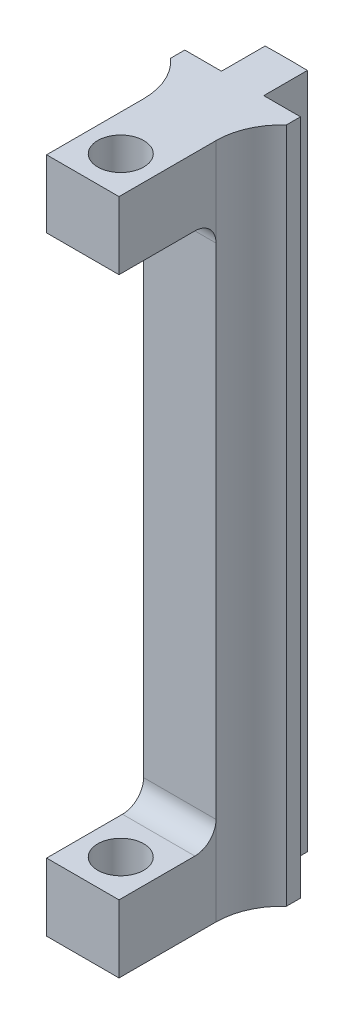
SolidWorks part; units mm, degrees
ref_plane "Front Plane" through (0, 0, 0) normal (0, 0, 1) x (1, 0, 0)
ref_plane "Top Plane" through (0, 0, 0) normal (0, 1, 0) x (1, 0, 0)
ref_plane "Right Plane" through (0, 0, 0) normal (1, 0, 0) x (0, 0, -1)
sketch "Sketch1" plane through (0, 0, 0) normal (0, 1, 0) x (1, 0, 0)
  line L0 (-2.7181, 75.8155) -> (2.7181, 75.8155)
  line L1 (8.1401, 80.7182) -> (8.1401, 83.4238)
  line L2 (-8.1401, 80.7182) -> (-8.1401, 83.4238)
  line L3 (0, 75.8155) -> (0, 87.8958) construction
  line L4 (2.7181, 75.8155) -> (2.7181, 62.9548) construction
  arc A0 (2.7181, 75.8155) -> (8.1401, 80.7182) centre (7.6457, 75.8155) cw
  arc A1 (8.1401, 83.4238) -> (-8.1401, 83.4238) centre (0, 0) ccw
  arc A2 (-2.7181, 75.8155) -> (-8.1401, 80.7182) centre (-7.6457, 75.8155) ccw
  arc A3 (8.1401, 80.7182) -> (20.3966, 78.5217) centre (0, 0) cw construction
  dimension "D2" = 81.1276
  dimension "D3" = 83.82
  dimension "D4" = 4.9276
  dimension "D1" = 2.7181
extrude "Boss-Extrude1" add sketch "Sketch1" against normal blind 50.8
sketch "Sketch3" plane through (0, 0, 0) normal (0, 1, 0) x (1, 0, 0)
  line L0 (-4.3408, 80.5281) -> (-1.5875, 80.5281)
  line L1 (-2.7181, 75.8155) -> (2.7181, 75.8155) construction
  line L2 (0, 83.82) -> (0, 75.8155) construction
  line L3 (-4.3408, 80.5281) -> (-4.3408, 76.768)
  line L4 (-4.3408, 76.768) -> (-9.7396, 76.768)
  line L5 (-9.7396, 76.768) -> (-9.7396, 86.1044)
  line L6 (-4.5117, 83.6985) -> (-4.3408, 80.5281) construction
  line L7 (-4.5117, 83.6985) -> (46.925, 86.4711) construction
  line L8 (0, 83.82) -> (-1.5875, 83.82)
  line L9 (-3.175, 86.1044) -> (-9.7396, 86.1044)
  line L10 (-1.5875, 83.82) -> (-1.5875, 80.5281)
  arc A0 (8.1401, 83.4238) -> (-8.1401, 83.4238) centre (0, 0) ccw construction
  arc A1 (-2.7181, 75.8155) -> (-8.1401, 80.7182) centre (-7.6457, 75.8155) ccw construction
  point P14 (-4.3408, 79.4704)
  dimension "D1" = 3.175
  dimension "D2" = 1.5875
extrude "Cut-Extrude1" cut sketch "Sketch3" against normal through all
mirror "Mirror2" about plane through (0, 0, 0) normal (1, 0, 0) of "Cut-Extrude1"
sketch "Sketch2" plane through (0, 0, 0) normal (0, 1, 0) x (1, 0, 0)
  line L1 (2.7181, 75.8155) -> (-2.7181, 75.8155)
  line L2 (2.7181, 75.8155) -> (2.7181, 68.5315)
  line L3 (2.7181, 68.5315) -> (-2.7181, 68.5315)
  line L4 (-2.7181, 75.8155) -> (-2.7181, 68.5315)
  dimension "D1" = 7.2839
extrude "Boss-Extrude2" add sketch "Sketch2" against normal blind 5.08
fillet "Fillet1" radius 1.5875 1 edges at (0, -5.08, -75.8155)
ref_plane "midplane" through (0, -25.4, 0) normal (0, -1, 0) x (-1, 0, 0)
mirror "Mirror1" about plane through (0, -25.4, 0) normal (0, -1, 0) of "Boss-Extrude2", "Fillet1"
hole_wizard "#4 Clearance Hole1" positions "Sketch4" profile "Sketch5" hole size "#4" standard "ANSI Inch" end condition through all
sketch "Sketch4" plane through (0, 0, 0) normal (0, 1, 0) x (1, 0, 0)
  line L0 (0, 68.5315) -> (0, 74.228) construction
  line L2 (-2.7181, 68.5315) -> (2.7181, 68.5315) construction
  line L3 (-2.7181, 74.228) -> (2.7181, 74.228) construction
  point P0 (0, 71.3797)
sketch "Sketch5" plane through (0, 0, -71.3797) normal (1, 0, 0) x (0, 0, 1)
  line L0 (0, 0) -> (0, 50.8)
  line L1 (0, 50.8) -> (1.7272, 50.8)
  line L2 (1.7272, 50.8) -> (1.7272, 0)
  line L5 (1.7272, 0) -> (0, 0)
  line L11 (0, -6.35) -> (0, 107.95) construction
  dimension "Thru Hole Dia." = 3.4544
  dimension "Thru Hole Depth" = 50.8
